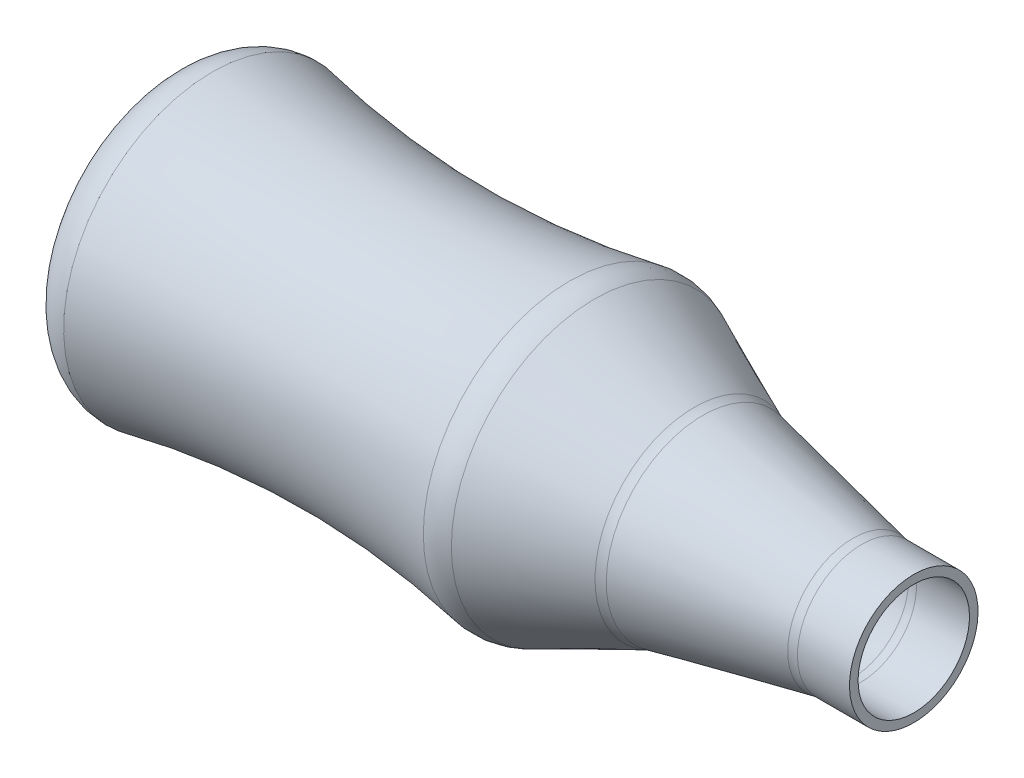
SolidWorks part; units mm, degrees
ref_plane "Front Plane" through (0, 0, 0) normal (0, 0, 1) x (1, 0, 0)
ref_plane "Top Plane" through (0, 0, 0) normal (0, 1, 0) x (1, 0, 0)
ref_plane "Right Plane" through (0, 0, 0) normal (1, 0, 0) x (0, 0, -1)
sketch "Sketch1" plane through (0, 0, 0) normal (0, 0, 1) x (1, 0, 0)
  line L0 (0, 0) -> (-173.75, 0) construction
  line L1 (-173.75, -24.705) -> (-173.75, 24.705)
  line L2 (-77.37, 34.705) -> (-50.28, 22.75)
  line L3 (-50.28, 22.75) -> (-13.19, 15)
  line L4 (0, 15) -> (0, -15)
  line L5 (-13.19, 15) -> (0, 15)
  line L6 (-13.19, -15) -> (0, -15)
  line L7 (-50.28, -22.75) -> (-13.19, -15)
  line L8 (-77.37, -34.705) -> (-50.28, -22.75)
  arc A0 (-173.75, 24.705) -> (-163.75, 34.705) centre (-163.75, 24.705) cw
  arc A1 (-163.75, 34.705) -> (-77.37, 34.705) centre (-120.56, 250.4239) ccw
  arc A2 (-163.75, -34.705) -> (-77.37, -34.705) centre (-120.56, -250.4239) cw
  arc A3 (-173.75, -24.705) -> (-163.75, -34.705) centre (-163.75, -24.705) ccw
  point P6 (0, 0)
  point P11 (-120.56, 30.4239)
  point P21 (0, 0)
  point P22 (0, 0)
  point P23 (0, 0)
  point P24 (0, 0)
  point P25 (-77.37, 34.705)
  point P26 (0, 0)
  point P27 (-77.37, 34.705)
  point P28 (0, 0)
  point P29 (0, 0)
  point P30 (-163.75, 34.705)
  point P31 (0, 0)
  point P32 (0, 0)
  point P33 (-77.37, 34.705)
  point P34 (-77.37, 34.705)
  point P35 (0, 0)
  point P36 (0, 0)
  dimension "D1" = 10
  dimension "D6" = 220
  dimension "D2" = 86.38
  dimension "D3" = 27.09
  dimension "D4" = 37.09
  dimension "D5" = 13.19
  dimension "D7" = 69.41
  dimension "D8" = 45.5
  dimension "D9" = 30
revolve "Revolve1" add sketch "Sketch1" angle 360 about L0 region at (-97.0706, 14.4594, 0)
shell "Shell2" thickness 2 removed face at (-173.75, 24.705, 0) removed face at (0, 15, 0)
ref_plane "Plane1" through (-173.75, 0, 0) normal (1, 0, 0) x (0, 0, -1)
sketch "Sketch2" plane through (-173.75, 0, 0) normal (1, 0, 0) x (0, 0, -1)
  circle A2 centre (0, 0) radius 24.705 construction
  circle A3 centre (0, 0) radius 24.705
extrude "Boss-Extrude1" add sketch "Sketch2" along normal blind 2
fillet "Fillet1" radius 10 3 edges at (-50.28, 22.75, 0) (-13.19, 15, 0) (-77.37, 34.705, 0)
fillet "Fillet2" radius 10 1 edges at (-13.3967, -13, 0)
